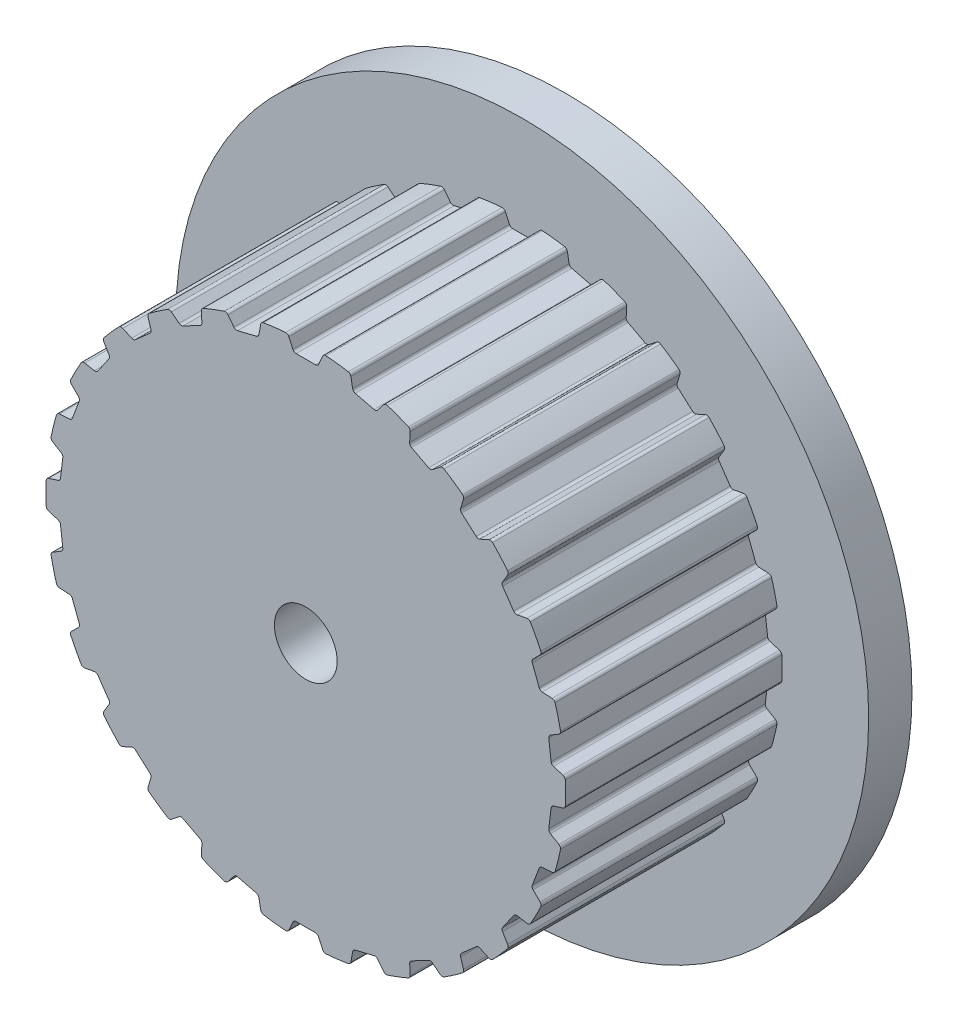
SolidWorks part; units mm, degrees
ref_plane "Front Plane" through (0, 0, 0) normal (0, 0, 1) x (1, 0, 0)
ref_plane "Top Plane" through (0, 0, 0) normal (0, 1, 0) x (1, 0, 0)
ref_plane "Right Plane" through (0, 0, 0) normal (1, 0, 0) x (0, 0, -1)
sketch "Sketch1" plane through (0, 0, 0) normal (0, 0, 1) x (1, 0, 0)
  circle A0 centre (0, 0) radius 12.7
  dimension "D1" = 25.4
extrude "Boss-Extrude1" add sketch "Sketch1" along normal blind 1.5875
sketch "Sketch2" plane through (0, 0, 1.5875) normal (0, 0, 1) x (1, 0, 0)
  circle A0 centre (0, 0) radius 9.525
  dimension "D1" = 19.05
extrude "Boss-Extrude2" add sketch "Sketch2" along normal blind 7.9375
sketch "Sketch3" plane through (0, 0, 9.525) normal (0, 0, 1) x (1, 0, 0)
  circle A0 centre (0, 0) radius 1.15
  dimension "D1" = 2.3
extrude "Cut-Extrude1" cut sketch "Sketch3" against normal through all
sketch "Sketch4" plane through (0, 0, 9.525) normal (0, 0, 1) x (1, 0, 0)
  line L0 (0, 9.017) -> (0, 9.525) construction
  line L1 (-0.3556, 9.017) -> (0.3556, 9.017)
  line L2 (0.4714, 9.0919) -> (0.6198, 9.4217)
  line L3 (-0.7356, 9.4966) -> (0.7356, 9.4966)
  line L4 (-0.4714, 9.0919) -> (-0.6198, 9.4217)
  line L6 (-0.7356, 9.4966) -> (0.7356, 9.4966)
  line L7 (-0.7356, 9.4966) -> (-0.7356, 10.1316)
  line L8 (-0.7356, 10.1316) -> (0.7356, 10.1316)
  line L9 (0.7356, 9.4966) -> (0.7356, 10.1316)
  circle A0 centre (0, 0) radius 9.525 construction
  arc A1 (0.7356, 9.4966) -> (0.6198, 9.4217) centre (0.7356, 9.3696) ccw
  arc A2 (0.3556, 9.017) -> (0.4714, 9.0919) centre (0.3556, 9.144) ccw
  arc A3 (-0.7356, 9.4966) -> (-0.6198, 9.4217) centre (-0.7356, 9.3696) cw
  arc A4 (-0.3556, 9.017) -> (-0.4714, 9.0919) centre (-0.3556, 9.144) cw
  point P13 (0, 9.4966)
  point P18 (0.6355, 9.5038)
  point P21 (0.4157, 9.0932)
  dimension "D1" = 0.127
  dimension "D2" = 0.127
  dimension "D3" = 0.508
  dimension "D4" = 0.635
  dimension "D5" = 0.3616
  dimension "D6" = 0.7112
extrude "Cut-Extrude2" cut sketch "Sketch4" against normal up to surface (7.9375 mm away) contours L3 A1 L2 A2 L1 A4 L4 A3 | L7 L6 L9 L8 up to face at (9.525, 0, 1.5875)
pattern_circular "CirPattern1" count 26 over 360 about axis through (0, 0, 1.5875) along (0, 0, 1) of "Cut-Extrude2"
